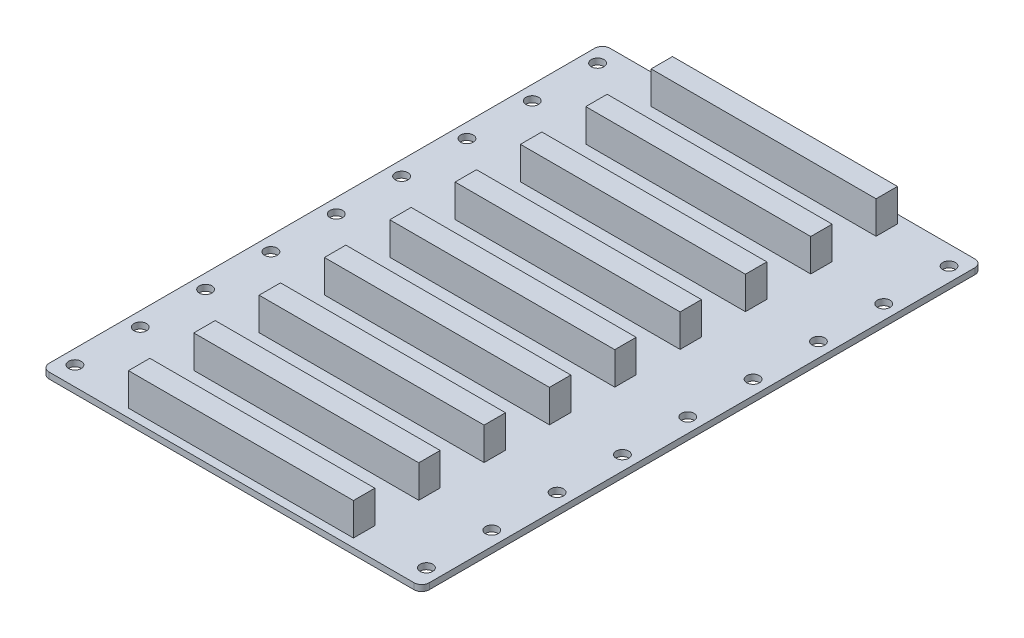
SolidWorks part; units mm, degrees
ref_plane "Front Plane" through (0, 0, 0) normal (0, 0, 1) x (1, 0, 0)
ref_plane "Top Plane" through (0, 0, 0) normal (0, 1, 0) x (1, 0, 0)
ref_plane "Right Plane" through (0, 0, 0) normal (1, 0, 0) x (0, 0, -1)
sketch "Sketch1" plane through (0, 0, 0) normal (0, 1, 0) x (1, 0, 0)
  line L1 (-49.75, -73.4) -> (49.75, -73.4)
  line L2 (-49.75, -73.4) -> (-49.75, 73.4)
  line L3 (-49.75, 73.4) -> (49.75, 73.4)
  line L4 (49.75, -73.4) -> (49.75, 73.4)
  line L5 (-49.75, -73.4) -> (49.75, 73.4) construction
  line L6 (-49.75, 73.4) -> (49.75, -73.4) construction
  point P0 (0, 0)
  dimension "D1" = 99.5
  dimension "D2" = 146.8
extrude "Boss-Extrude1" add sketch "Sketch1" along normal blind 1.6
sketch "Sketch3" plane through (0, 1.6, 0) normal (0, 1, 0) x (1, 0, 0)
  line L0 (0, 73.4) -> (0, -73.4) construction
  line L1 (49.75, 73.4) -> (-49.75, 73.4) construction
  line L2 (-49.75, -73.4) -> (49.75, -73.4) construction
  line L4 (-49.75, 73.4) -> (-49.75, -73.4) construction
  circle A1 centre (-46, -68.4) radius 1.65
  circle A3 centre (-46, -51.3) radius 1.65
  circle A4 centre (-46, -34.2) radius 1.65
  circle A5 centre (-46, -17.1) radius 1.65
  circle A6 centre (-46, 0) radius 1.65
  circle A7 centre (-46, 17.1) radius 1.65
  circle A8 centre (-46, 34.2) radius 1.65
  circle A9 centre (-46, 51.3) radius 1.65
  circle A10 centre (-46, 68.4) radius 1.65
  circle A11 centre (46, 68.4) radius 1.65
  circle A12 centre (46, 51.3) radius 1.65
  circle A13 centre (46, 34.2) radius 1.65
  circle A14 centre (46, 17.1) radius 1.65
  circle A15 centre (46, 0) radius 1.65
  circle A16 centre (46, -17.1) radius 1.65
  circle A17 centre (46, -34.2) radius 1.65
  circle A18 centre (46, -51.3) radius 1.65
  circle A19 centre (46, -68.4) radius 1.65
  dimension "D1" = 3.3
  dimension "D2" = 3.75
  dimension "D3" = 9
  dimension "D4" = 17.1
  dimension "D5" = 5
extrude "Cut-Extrude2" cut sketch "Sketch3" against normal up to surface (1.6 mm away) up to face at (0, 0, 0)
sketch "Sketch4" plane through (0, 1.6, 0) normal (0, 1, 0) x (1, 0, 0)
  line L0 (-29.195, -54.1) -> (-29.195, -48.5)
  line L1 (-29.195, -71.2) -> (29.695, -71.2)
  line L2 (-29.195, -71.2) -> (-29.195, -65.6)
  line L3 (-29.195, -65.6) -> (29.695, -65.6)
  line L4 (29.695, -71.2) -> (29.695, -65.6)
  line L5 (-29.195, -71.2) -> (29.695, -65.6) construction
  line L6 (-29.195, -65.6) -> (29.695, -71.2) construction
  line L7 (-49.75, -73.4) -> (49.75, -73.4) construction
  line L8 (49.75, -73.4) -> (49.75, 73.4) construction
  line L9 (-29.195, -54.1) -> (29.695, -54.1)
  line L10 (29.695, -54.1) -> (29.695, -48.5)
  line L11 (-29.195, -48.5) -> (29.695, -48.5)
  line L12 (-29.195, -37) -> (-29.195, -31.4)
  line L13 (-29.195, -37) -> (29.695, -37)
  line L14 (29.695, -37) -> (29.695, -31.4)
  line L15 (-29.195, -31.4) -> (29.695, -31.4)
  line L16 (-29.195, -19.9) -> (-29.195, -14.3)
  line L17 (-29.195, -19.9) -> (29.695, -19.9)
  line L18 (29.695, -19.9) -> (29.695, -14.3)
  line L19 (-29.195, -14.3) -> (29.695, -14.3)
  line L20 (-29.195, -2.8) -> (-29.195, 2.8)
  line L21 (-29.195, -2.8) -> (29.695, -2.8)
  line L22 (29.695, -2.8) -> (29.695, 2.8)
  line L23 (-29.195, 2.8) -> (29.695, 2.8)
  line L24 (-29.195, 14.3) -> (-29.195, 19.9)
  line L25 (-29.195, 14.3) -> (29.695, 14.3)
  line L26 (29.695, 14.3) -> (29.695, 19.9)
  line L27 (-29.195, 19.9) -> (29.695, 19.9)
  line L28 (-29.195, 31.4) -> (-29.195, 37)
  line L29 (-29.195, 31.4) -> (29.695, 31.4)
  line L30 (29.695, 31.4) -> (29.695, 37)
  line L31 (-29.195, 37) -> (29.695, 37)
  line L32 (-29.195, 48.5) -> (-29.195, 54.1)
  line L33 (-29.195, 48.5) -> (29.695, 48.5)
  line L34 (29.695, 48.5) -> (29.695, 54.1)
  line L35 (-29.195, 54.1) -> (29.695, 54.1)
  line L36 (-29.195, 65.6) -> (-29.195, 71.2)
  line L37 (-29.195, 65.6) -> (29.695, 65.6)
  line L38 (29.695, 65.6) -> (29.695, 71.2)
  line L39 (-29.195, 71.2) -> (29.695, 71.2)
  point P0 (0.25, -68.4)
  dimension "D1" = 5.6
  dimension "D2" = 58.89
  dimension "D3" = 5
  dimension "D4" = 49.5
  dimension "D6" = 11.5
  dimension "D5" = 9
extrude "Boss-Extrude2" add sketch "Sketch4" along normal blind 8.5
fillet "Fillet2" radius 2 4 edges at (-49.75, 0.8, -73.4) (49.75, 0.8, -73.4) (49.75, 0.8, 73.4) (-49.75, 0.8, 73.4)
